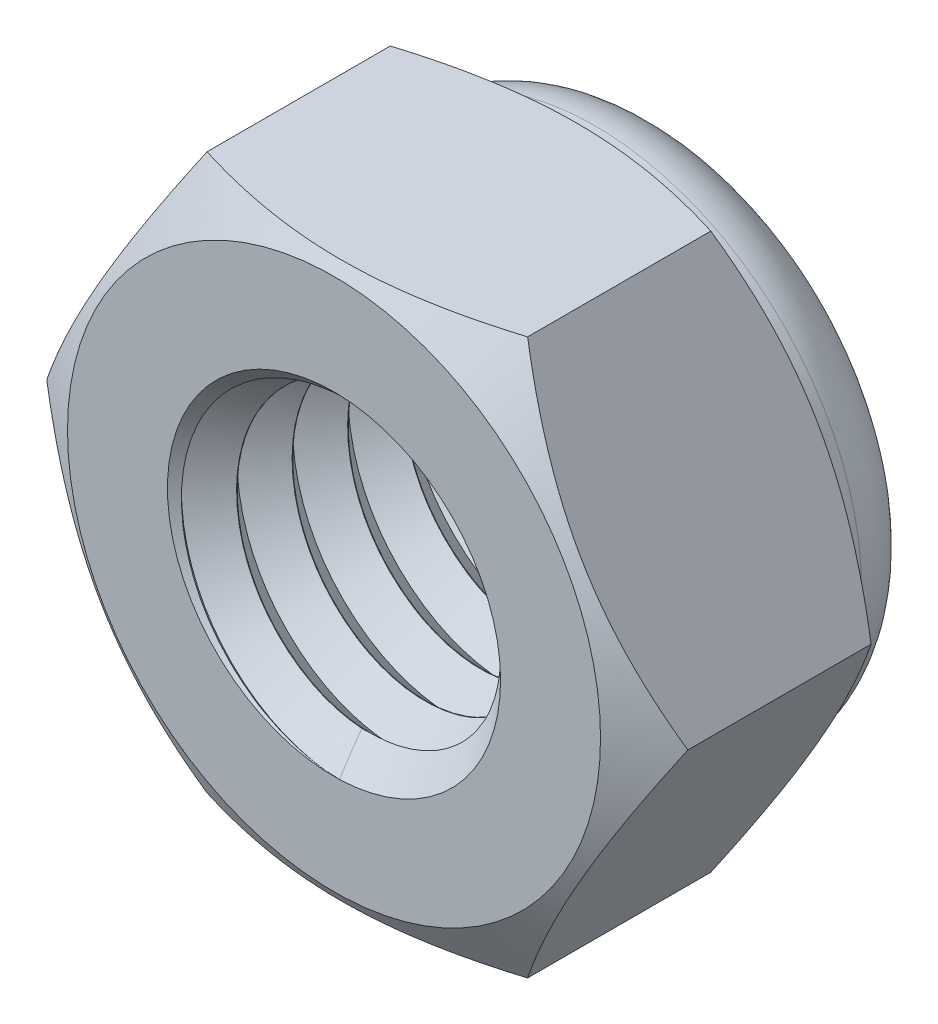
SolidWorks part; units mm, degrees
material "AISI 1045 Aço, trefilado"
ref_plane "Plano frontal" through (0, 0, 0) normal (0, 0, 1) x (1, 0, 0)
ref_plane "Plano superior" through (0, 0, 0) normal (0, 1, 0) x (1, 0, 0)
ref_plane "Plano direito" through (0, 0, 0) normal (1, 0, 0) x (0, 0, -1)
sketch "Esboço1" plane through (0, 0, 0) normal (0, 0, 1) x (1, 0, 0)
  line L1 (5.7735, 0) -> (2.8868, 5)
  line L2 (2.8868, 5) -> (-2.8868, 5)
  line L3 (-2.8868, 5) -> (-5.7735, 0)
  line L4 (-5.7735, 0) -> (-2.8868, -5)
  line L5 (-2.8868, -5) -> (2.8868, -5)
  line L6 (2.8868, -5) -> (5.7735, 0)
  circle A0 centre (0, 0) radius 5 construction
  circle A1 centre (0, 0) radius 2.5
  dimension "D2" = 5
  dimension "D1" = 10
extrude "Ressalto-extrusão1" add sketch "Esboço1" along normal blind 4.5
chamfer "Chanfro1" distance 0.5 angle 45 1 edges at (2.5, 0, 4.5)
sketch "Esboço2" plane through (0, 0, 0) normal (0, 1, 0) x (1, 0, 0)
  line L0 (0, 0) -> (0, 2.2781) construction
  line L1 (-4.8, 0) -> (-4.8, 0.2)
  line L2 (-5.7735, 0) -> (-2.8868, 0) construction
  line L3 (-3.5, 1.5) -> (-3.1, 1.5)
  line L4 (-4.6, 0) -> (-4.6, 0.2)
  line L5 (-3.5, 1.3) -> (-3.1, 1.3)
  line L6 (-3.1, 1.5) -> (-3.1, 1.3)
  line L7 (-4.8, 0) -> (-4.6, 0)
  arc A0 (-4.8, 0.2) -> (-3.5, 1.5) centre (-3.5, 0.2) cw
  arc A1 (-4.6, 0.2) -> (-3.5, 1.3) centre (-3.5, 0.2) cw
  dimension "D1" = 9.6
  dimension "D2" = 1.5
  dimension "D3" = 0.2
  dimension "D4" = 6.2
  dimension "D5" = 0.2
revolve "Revolução1" add sketch "Esboço2" angle 360 about L0
sketch "Esboço3" plane through (0, 0, 0) normal (0, 1, 0) x (1, 0, 0)
  line L0 (0, 0) -> (0, 2.0346) construction
  line L1 (-4.8, 0.2) -> (-4.8, 0) construction
  line L2 (-4.8, 0.2) -> (-4.8, 0) construction
  line L3 (-3.5, 1.5) -> (-3.1, 1.5) construction
  line L4 (3.5, 1.5) -> (-3.5, 1.5) construction
  line L5 (3.1, 1.5) -> (-3.1, 1.5) construction
  line L6 (-3.5, 1.28) -> (-2.5, 1.28)
  line L7 (-4.58, 0.2) -> (-4.58, 0.02)
  line L8 (-3.5, 1.28) -> (-3.1, 1.28) construction
  line L9 (-5.7735, 0) -> (-2.8868, 0) construction
  line L12 (-2.5, 0.02) -> (-2.5, 1.28)
  line L13 (-4.58, 0.02) -> (-2.5, 0.02)
  line L14 (-4.58, 0.2) -> (-4.58, 0) construction
  arc A0 (-3.5, 1.5) -> (-4.8, 0.2) centre (-3.5, 0.2) ccw construction
  arc A1 (-3.5, 1.5) -> (-4.8, 0.2) centre (-3.5, 0.2) ccw construction
  arc A2 (-3.5, 1.28) -> (-4.58, 0.2) centre (-3.5, 0.2) ccw
  dimension "D1" = 0.4
  dimension "D3" = 5
  dimension "D4" = 0.02
  dimension "D2" = 0.22
revolve "Revolução2" add sketch "Esboço3" angle 360 about L0
sketch "Esboço4" plane through (0, 0, 0) normal (0, 1, 0) x (1, 0, 0)
  line L0 (0, 0) -> (0, -6.1362) construction
  line L1 (4.8, 0) -> (5.7735, 0)
  line L2 (4.8, 0) -> (-4.8, 0) construction
  line L3 (2.8868, 0) -> (5.7735, 0) construction
  line L4 (5.7735, 0) -> (5.7735, -0.6)
  line L5 (5.7735, -0.6) -> (4.8, 0)
  line L6 (4.8, -4.5) -> (5.7735, -4.5)
  line L7 (2.8868, -4.5) -> (5.7735, -4.5) construction
  line L8 (5.7735, -4.5) -> (5.7735, -3.9)
  line L9 (5.7735, -3.9) -> (4.8, -4.5)
  line L10 (5.7735, -4.5) -> (5.7735, 0) construction
  dimension "D1" = 9.6
  dimension "D3" = 0.6
  dimension "D4" = 0.6
revolve "Corte-Revolução1" cut sketch "Esboço4" angle 360 about L0
sketch "Esboço5" plane through (0, 0, 4.5) normal (0, 0, 1) x (1, 0, 0)
  circle A0 centre (0, 0) radius 3
  dimension "D1" = 6
curve "Hélice/Espiral1" pitch 1 height 8 radius 3 centre (0, 0, 4.5) axis (0, 0, -1) start towards (0, 1, 0)
sketch "Esboço6" plane through (0, 0, 0) normal (1, 0, 0) x (0, 0, -1)
  line L0 (-4.5, 2.5) -> (-5.49, 2.5)
  line L1 (-5.49, 2.5) -> (-4.995, 3)
  line L2 (-4.995, 3) -> (-4.5, 2.5)
  point P2 (-4.995, 2.5)
  point P4 (-4.5, 3)
  dimension "D1" = 0.99
  dimension "D2" = 0.5
sweep "Varredura de corte1" cut profiles "Esboço6" path "Hélice/Espiral1" align with end faces yes
